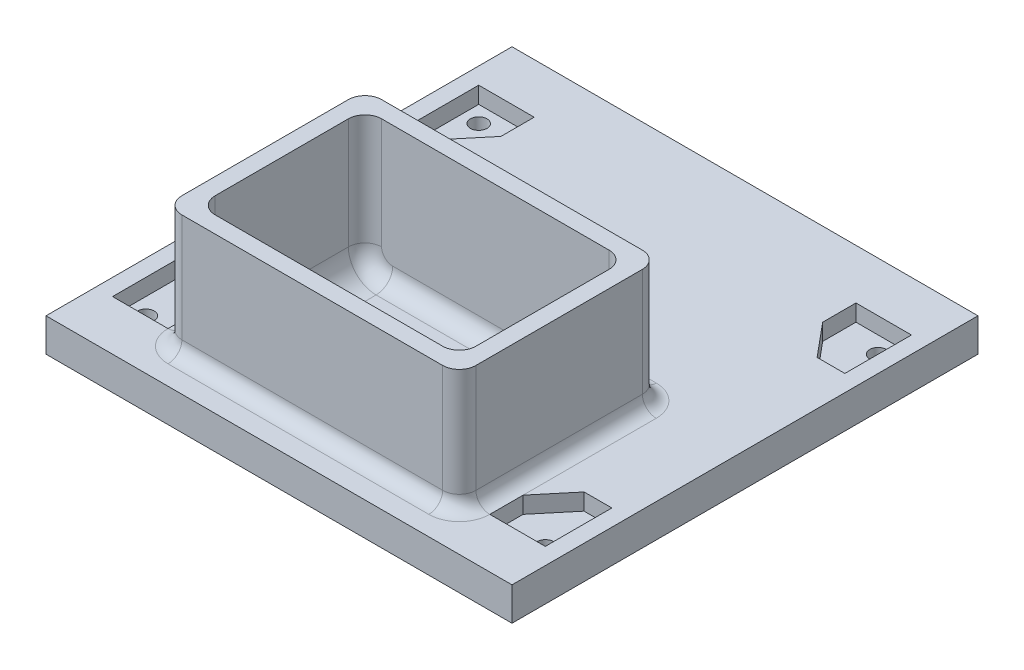
SolidWorks part; units mm, degrees
ref_plane "Front Plane" through (0, 0, 0) normal (0, 0, 1) x (1, 0, 0)
ref_plane "Top Plane" through (0, 0, 0) normal (0, 1, 0) x (1, 0, 0)
ref_plane "Right Plane" through (0, 0, 0) normal (1, 0, 0) x (0, 0, -1)
sketch "Sketch1" plane through (0, 0, 0) normal (0, 1, 0) x (1, 0, 0)
  line L1 (0, 0) -> (84, 0)
  line L2 (0, 0) -> (0, 84)
  line L3 (0, 84) -> (84, 84)
  line L4 (84, 0) -> (84, 84)
  dimension "D1" = 84
  dimension "D2" = 84
extrude "Boss-Extrude1" add sketch "Sketch1" along normal blind 6
sketch "Sketch2" plane through (0, 6, 0) normal (0, 1, 0) x (1, 0, 0)
  line L0 (84, 84) -> (0, 84) construction
  line L1 (0, 84) -> (0, 0) construction
  line L2 (0, 0) -> (84, 0) construction
  line L3 (84, 0) -> (84, 84) construction
  circle A0 centre (6, 72) radius 1.5
  circle A1 centre (6, 12) radius 1.5
  circle A2 centre (78, 12) radius 1.5
  circle A3 centre (78, 72) radius 1.5
  dimension "D1" = 3
  dimension "D2" = 3
  dimension "D3" = 3
  dimension "D4" = 3
  dimension "D6" = 6
  dimension "D7" = 12
  dimension "D8" = 6
  dimension "D9" = 6
  dimension "D10" = 12
  dimension "D11" = 6
  dimension "D5" = 12
  dimension "D12" = 12
extrude "Cut-Extrude1" cut sketch "Sketch2" against normal through all
ref_plane "Plane1" through (0, 0, -42) normal (0, 0, 1) x (1, 0, 0)
sketch "Sketch4" plane through (0, 6, 0) normal (0, 1, 0) x (1, 0, 0)
  line L0 (3, 21) -> (3, 9)
  line L1 (3, 9) -> (13, 9)
  line L2 (13, 15) -> (8, 21)
  line L3 (3, 21) -> (8, 21)
  line L4 (8, 21) -> (13, 15)
  line L5 (13, 15) -> (13, 9)
  line L6 (0, 84) -> (0, 0) construction
  line L7 (0, 0) -> (84, 0) construction
  circle A0 centre (6, 12) radius 1.5
  circle A1 centre (6, 12) radius 1.5 construction
  circle M21 centre (6, 12) radius 1.5
  dimension "D1" = 3
  dimension "D2" = 9
  dimension "D3" = 12
  dimension "D4" = 10
  dimension "D5" = 6
  dimension "D6" = 5
extrude "Cut-Extrude4" cut sketch "Sketch4" against normal blind 3 contours L5 L2 L3 L0 L1 M21 region at (7.6338, 6, -14.6039)
mirror "Mirror2" about plane through (0, 0, -42) normal (0, 0, 1) of "Cut-Extrude4"
ref_plane "Plane2" through (42, 0, 0) normal (-1, 0, 0) x (0, 0, 1)
mirror "Mirror3" about plane through (42, 0, 0) normal (-1, 0, 0) of "Mirror2"
sketch "Sketch5" plane through (0, 6, 0) normal (0, 1, 0) x (1, 0, 0)
  line L0 (15.5, 42) -> (15.5, 6)
  line L1 (15.5, 42) -> (68.5, 42)
  line L2 (15.5, 6) -> (68.5, 6)
  line L3 (68.5, 42) -> (68.5, 6)
  line L4 (15.5, 42) -> (68.5, 6) construction
  line L5 (15.5, 6) -> (68.5, 42) construction
  line L6 (42, 3.3) -> (42, -3.3) construction
  line L7 (-3.3, 42) -> (3.3, 42) construction
  point P1 (42, 24)
  dimension "D1" = 53
  dimension "D2" = 36
extrude "Boss-Extrude2" add sketch "Sketch5" along normal blind 22
sketch "Sketch6" plane through (0, 28, 0) normal (0, 1, 0) x (1, 0, 0)
  line L14 (65.5, 39) -> (18.5, 39)
  line L15 (18.5, 39) -> (18.5, 9)
  line L16 (18.5, 9) -> (65.5, 9)
  line L17 (65.5, 9) -> (65.5, 39)
  line L18 (65.5, 39) -> (18.5, 39)
  line L19 (18.5, 39) -> (18.5, 9)
  line L20 (18.5, 9) -> (65.5, 9)
  line L21 (65.5, 9) -> (65.5, 39)
  dimension "D1" = 3
extrude "Cut-Extrude5" cut sketch "Sketch6" against normal blind 25
fillet "Fillet1" radius 3 10 edges at (65.5, 15.5, -39) (18.5, 15.5, -39) (65.5, 15.5, -9) (18.5, 15.5, -9) (15.5, 17, -42) (68.5, 17, -6) (68.5, 17, -42) (15.5, 17, -6) (42, 3, -9) (42, 3, -39)
fillet "Fillet2" radius 5 6 edges at (19.3787, 3.8787, -9.8787) (19.3787, 3.8787, -38.1213) (64.6213, 3.8787, -38.1213) (64.6213, 3.8787, -9.8787) (65.5, 3, -24) (18.5, 3, -24)
fillet "Fillet3" radius 2.5 8 edges at (67.6213, 6, -6.8787) (67.6213, 6, -41.1213) (16.3787, 6, -6.8787) (16.3787, 6, -41.1213) (15.5, 6, -24) (42, 6, -42) (68.5, 6, -24) (42, 6, -6)
